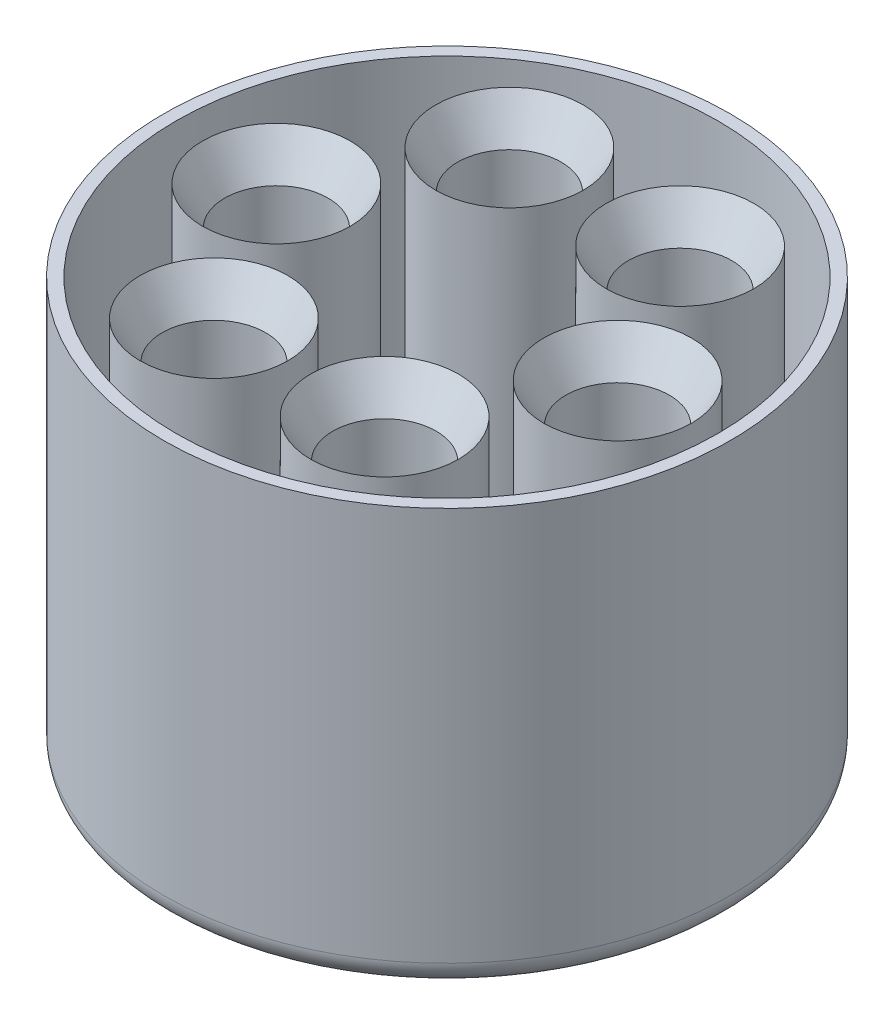
SolidWorks part; units mm, degrees
ref_plane "Front Plane" through (0, 0, 0) normal (0, 0, 1) x (1, 0, 0)
ref_plane "Top Plane" through (0, 0, 0) normal (0, 1, 0) x (1, 0, 0)
ref_plane "Right Plane" through (0, 0, 0) normal (1, 0, 0) x (0, 0, -1)
sketch "Sketch2" plane through (0, 0, 0) normal (0, 1, 0) x (1, 0, 0)
  line L0 (0, 0) -> (0, -0.696) construction
  line L1 (0, 0) -> (-1.0552, 0) construction
  line L3 (-34.641, 0) -> (-17.3205, -30)
  line L4 (-17.3205, -30) -> (17.3205, -30)
  line L5 (17.3205, -30) -> (34.641, 0)
  line L6 (34.641, 0) -> (17.3205, 30)
  line L7 (17.3205, 30) -> (-17.3205, 30)
  line L8 (-17.3205, 30) -> (-34.641, 0)
  circle A0 centre (-34.641, 0) radius 15
  circle A1 centre (0, 0) radius 30 construction
  circle A2 centre (-17.3205, 30) radius 15
  circle A3 centre (17.3205, 30) radius 15
  circle A4 centre (34.641, 0) radius 15
  circle A5 centre (17.3205, -30) radius 15
  circle A6 centre (-17.3205, -30) radius 15
  circle A7 centre (0, 0) radius 55
  circle A8 centre (0, 0) radius 57.5
  circle A9 centre (-17.3205, 30) radius 10.5
  circle A10 centre (-34.641, 0) radius 10.5
  circle A11 centre (-17.3205, -30) radius 10.5
  circle A12 centre (17.3205, -30) radius 10.5
  circle A13 centre (34.641, 0) radius 10.5
  circle A14 centre (17.3205, 30) radius 10.5
  dimension "D1" = 30
  dimension "D3" = 110
  dimension "D2" = 60
  dimension "D4" = 2.5
  dimension "D5" = 4.5
extrude "Boss-Extrude1" add sketch "Sketch2" along normal blind 75 contours A8 A7 | L3 A0 L8 | L8 A0 L3 | L7 A2 L8 | L8 A2 L7 | L4 A6 L3 | L3 A6 L4 | L5 A5 L4 | L4 A5 L5 | L6 A4 L5 | L5 A4 L6 | L7 A3 L6 | L6 A3 L7 region at (-23.9874, 0, 0) region at (-28.5908, 0, 11.2293) region at (-11.9937, 0, 20.7737) region at (-24.0508, 0, 19.1633) region at (-24.6154, 0, -42.6351) region at (-11.9937, 0, -20.7737) region at (11.9937, 0, 20.7737) region at (4.5705, 0, 30.4103) region at (17.3205, 0, -44.5897) region at (11.9937, 0, -20.7737) region at (23.9874, 0, 0) region at (28.5908, 0, 11.2293) region at (-55.8737, 0, 0)
sketch "Sketch3" plane through (0, 0, 0) normal (0, -1, 0) x (1, 0, 0)
  circle A0 centre (0, 0) radius 57.5
  circle A1 centre (0, 0) radius 55 construction
  circle A2 centre (0, 0) radius 57.5 construction
extrude "Boss-Extrude2" add sketch "Sketch3" along normal blind 10
chamfer "Chamfer2" distance 5 angle 60 6 edges at (-17.3205, 75, -19.5) (-34.641, 75, 10.5) (-17.3205, 75, 40.5) (17.3205, 75, 40.5) (34.641, 75, 10.5) (17.3205, 75, -19.5) first distance on face at (-17.3205, 75, -19.5) first distance on face at (-34.641, 75, 15) first distance on face at (-17.3205, 75, 45) first distance on face at (17.3205, 75, 45) first distance on face at (34.641, 75, 15) first distance on face at (17.3205, 75, -15)
fillet "Fillet1" radius 5 1 edges at (0, -10, -57.5)
equation "\"C\"=30"
equation "\"D1@Sketch2\"=\"C\""
equation "\"H\"=75"
equation "\"D1@Boss-Extrude1\"=\"H\""
equation "\"D\"=110"
equation "\"D3@Sketch2\"=\"D\""
